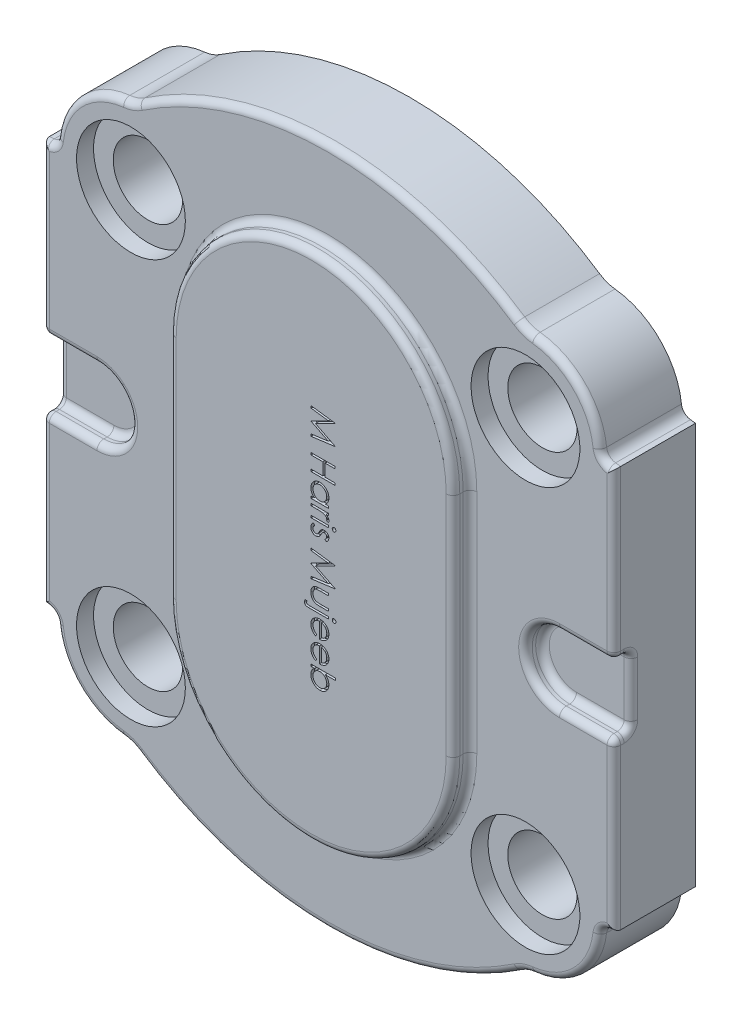
SolidWorks part; units mm, degrees
ref_plane "Ebene vorne" through (0, 0, 0) normal (0, 0, 1) x (1, 0, 0)
ref_plane "Ebene oben" through (0, 0, 0) normal (0, 1, 0) x (1, 0, 0)
ref_plane "Ebene rechts" through (0, 0, 0) normal (1, 0, 0) x (0, 0, -1)
sketch "Sketch1" plane through (0, 0, 0) normal (0, 0, 1) x (1, 0, 0)
  line L0 (-41.2554, 29.5859) -> (-42, 29.5)
  line L1 (-42, 29.5) -> (-42, -29.5)
  line L2 (0, 50) -> (0, 0) construction
  line L3 (42, 29.5) -> (42, -29.5)
  line L4 (41.2554, 29.5859) -> (42, 29.5)
  line L5 (55, 0) -> (-55, 0) construction
  line L6 (41.2554, -29.5859) -> (42, -29.5)
  line L7 (-41.2554, -29.5859) -> (-42, -29.5)
  arc A0 (27.8999, 41.4921) -> (-27.8999, 41.4921) centre (0, 0) ccw
  circle A2 centre (-29, 29.7308) radius 5.1
  arc A3 (-30.1618, 40.6693) -> (-39.9361, 30.9146) centre (-29, 29.7308) ccw
  arc A4 (-27.8999, 41.4921) -> (-30.1618, 40.6693) centre (-30.6899, 45.6413) cw
  arc A5 (-39.9361, 30.9146) -> (-41.2554, 29.5859) centre (-41.4274, 31.076) cw
  arc A6 (39.9361, 30.9146) -> (41.2554, 29.5859) centre (41.4274, 31.076) ccw
  arc A7 (27.8999, 41.4921) -> (30.1618, 40.6693) centre (30.6899, 45.6413) ccw
  arc A8 (30.1618, 40.6693) -> (39.9361, 30.9146) centre (29, 29.7308) cw
  circle A9 centre (29, 29.7308) radius 5.1
  circle A10 centre (29, -29.7308) radius 5.1
  arc A11 (30.1618, -40.6693) -> (39.9361, -30.9146) centre (29, -29.7308) ccw
  arc A12 (27.8999, -41.4921) -> (30.1618, -40.6693) centre (30.6899, -45.6413) cw
  arc A13 (39.9361, -30.9146) -> (41.2554, -29.5859) centre (41.4274, -31.076) cw
  arc A14 (-39.9361, -30.9146) -> (-41.2554, -29.5859) centre (-41.4274, -31.076) ccw
  arc A15 (-27.8999, -41.4921) -> (-30.1618, -40.6693) centre (-30.6899, -45.6413) ccw
  arc A16 (-30.1618, -40.6693) -> (-39.9361, -30.9146) centre (-29, -29.7308) cw
  circle A17 centre (-29, -29.7308) radius 5.1
  arc A18 (27.8999, -41.4921) -> (-27.8999, -41.4921) centre (0, 0) cw
  point P11 (-29, 40.7308)
  point P14 (-40, 29.7308)
  point P25 (40, 29.7308)
  point P26 (29, 40.7308)
  point P46 (42, 0)
  point P47 (-42, 0)
  dimension "D1" = 50
  dimension "D2" = 10.2
  dimension "D3" = 29
  dimension "D5" = 11
  dimension "D4" = 5
  dimension "D6" = 1.5
  dimension "D7" = 29.5
  dimension "D8" = 42
extrude "Boss-Extrude1" add sketch "Sketch1" along normal blind 12
sketch "Sketch4" plane through (0, 0, 12) normal (0, 0, 1) x (1, 0, 0)
  line L0 (0, -16.68) -> (0, 16.68) construction
  line L1 (-20.85, -16.68) -> (-20.85, 16.68)
  line L2 (20.85, -16.68) -> (20.85, 16.68)
  arc A0 (-20.85, -16.68) -> (20.85, -16.68) centre (0, -16.68) ccw
  arc A1 (20.85, 16.68) -> (-20.85, 16.68) centre (0, 16.68) ccw
  point P2 (0, 0)
  dimension "D1" = 41.7
  dimension "D2" = 16.68
extrude "Boss-Extrude2" add sketch "Sketch4" along normal blind 2.5
sketch "Sketch5" plane through (0, 0, 12) normal (0, 0, 1) x (1, 0, 0)
  line L0 (-42, 0) -> (-34, 0) construction
  line L1 (-42, 29.5) -> (-42, -29.5) construction
  line L2 (-42, 5) -> (-34, 5)
  line L3 (-34, -5) -> (-42, -5)
  line L4 (-42, 5) -> (-42, -5)
  arc A0 (-34, 5) -> (-34, -5) centre (-34, 0) cw
  dimension "D1" = 5
  dimension "D2" = 8
extrude "Cut-Extrude2" cut sketch "Sketch5" against normal blind 2.5
mirror "Mirror1" about plane through (0, 0, 0) normal (1, 0, 0) of "Cut-Extrude2"
fillet "Fillet1" radius 1 32 edges at (40.363, -30.0191, 12) (36.7703, -37.5168, 12) (28.9806, -40.9426, 12) (0, -50, 12) (-28.9806, -40.9426, 12) (-36.7703, -37.5168, 12) (-40.363, -30.0191, 12) (-42, -17.25, 12) (-38, -5, 12) (-29, 0, 12) (-38, 5, 12) (-42, 17.25, 12) (-40.363, 30.0191, 12) (-36.7703, 37.5168, 12) (-28.9806, 40.9426, 12) (0, 50, 12) (28.9806, 40.9426, 12) (36.7703, 37.5168, 12) (40.363, 30.0191, 12) (42, 17.25, 12) (38, 5, 12) (29, 0, 12) (38, -5, 12) (42, -17.25, 12) (0, 37.53, 12) (-20.85, 0, 12) (0, -37.53, 12) (20.85, 0, 12) (-34.1, -29.7308, 12) (23.9, 29.7308, 12) (-23.9, 29.7308, 12) (34.1, -29.7308, 12)
fillet "Fillet2" radius 1 20 edges at (41.7071, -5.2929, 11.7071) (41.7071, 5.2929, 11.7071) (-41.7071, 5.2929, 11.7071) (-41.7071, -5.2929, 11.7071) (42, -5, 10.25) (42, 5, 10.25) (-42, 5, 10.25) (-42, -5, 10.25) (-20.85, 0, 14.5) (0, 37.53, 14.5) (20.85, 0, 14.5) (0, -37.53, 14.5) (38, -5, 9.5) (29, 0, 9.5) (38, 5, 9.5) (42, 0, 9.5) (-38, 5, 9.5) (-29, 0, 9.5) (-38, -5, 9.5) (-42, 0, 9.5)
sketch "Sketch6" plane through (0, 0, 12) normal (0, 0, 1) x (1, 0, 0)
  circle A0 centre (-29, 29.7308) radius 8
  dimension "D1" = 16
extrude "Cut-Extrude3" cut sketch "Sketch6" against normal blind 2.5
mirror "Mirror2" about plane through (0, 0, 0) normal (0, 1, 0) of "Cut-Extrude3"
mirror "Mirror3" about plane through (0, 0, 0) normal (1, 0, 0) of "Mirror2", "Cut-Extrude3"
sketch "Sketch7" plane through (0, 0, 14.5) normal (0, 0, 1) x (1, 0, 0)
  line L0 (0, 25.3423) -> (0, -25.0194) construction
  text T0 "M Haris Mujeeb"
extrude "Cut-Extrude5" cut sketch "Sketch7" against normal offset from surface (0.5 mm away) 0.5 up to face at (0, 0, 14.5)
